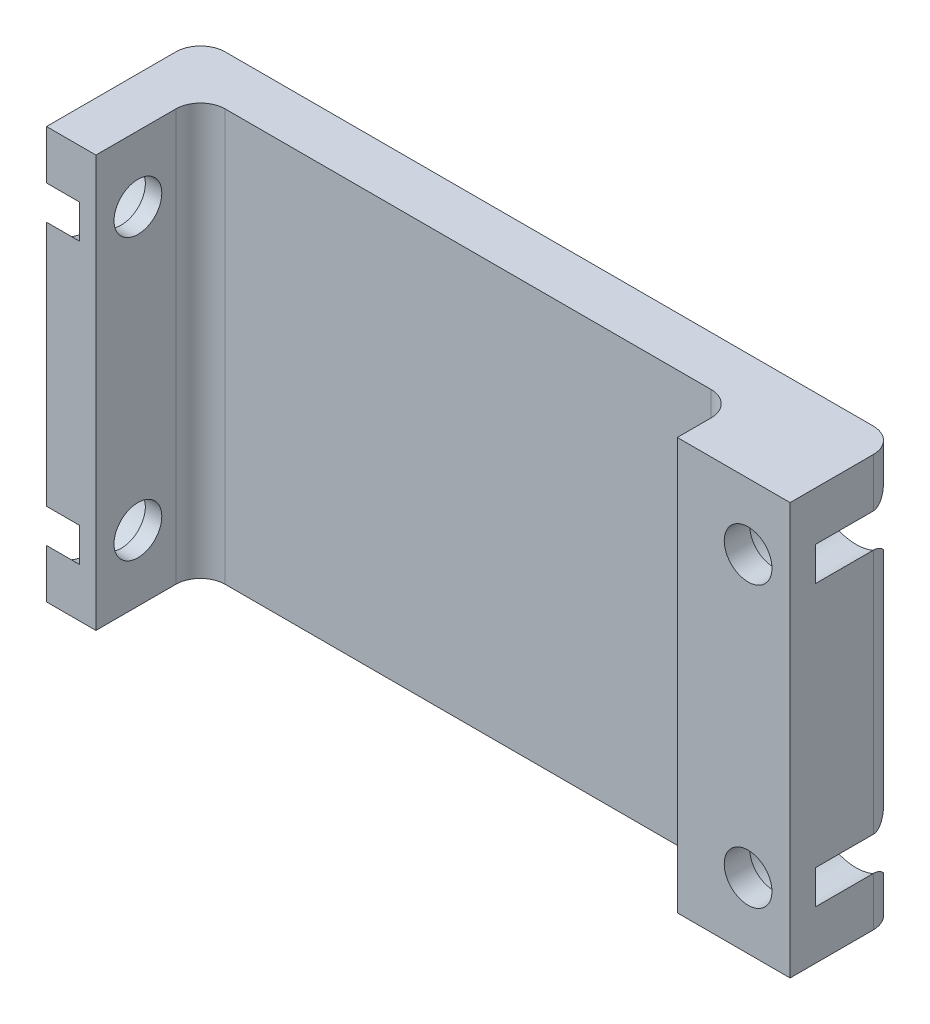
SolidWorks part; units mm, degrees
ref_plane "Plano frontal" through (0, 0, 0) normal (0, 0, 1) x (1, 0, 0)
ref_plane "Plano superior" through (0, 0, 0) normal (0, 1, 0) x (1, 0, 0)
ref_plane "Plano direito" through (0, 0, 0) normal (1, 0, 0) x (0, 0, -1)
sketch "Esboço2" plane through (0, 0, 0) normal (0, 0, 1) x (1, 0, 0)
  line L0 (0, 0) -> (0, -38.6) construction
  line L1 (-1.5, -22.5) -> (5.3501, -22.5)
  line L2 (-1.5, -22.5) -> (-1.5, 2.5)
  line L3 (-1.5, 2.5) -> (5.3501, 2.5)
  line L4 (5.3501, -22.5) -> (5.3501, 2.5)
  line L5 (2.8, -1.5) -> (2.8, 2.5) construction
  line L6 (2.8, -18.5) -> (2.8, -22.5) construction
  dimension "D1" = 0.25
  dimension "D2" = 4
  dimension "D3" = 1.5
extrude "Ressalto-extrusão2" add sketch "Esboço2" against normal offset from surface (3.55 mm away) 1 from offset 0.25 offset beyond the face yes offset against normal yes
sketch "Esboço3" plane through (0, 0, -3.8) normal (0, 0, -1) x (-1, 0, 0)
  line L0 (33.75, 0) -> (33.75, -38.6) construction
  line L1 (-5.3501, 2.5) -> (34, 2.5)
  line L2 (-5.3501, 2.5) -> (-5.3501, -22.5)
  line L3 (-5.3501, -22.5) -> (34, -22.5)
  line L4 (34, 2.5) -> (34, -22.5)
  line L5 (-5.3501, -22.5) -> (1.5, -22.5) construction
  dimension "D1" = 0.25
extrude "Ressalto-extrusão3" add sketch "Esboço3" along normal blind 3
sketch "Esboço4" plane through (-34, 0, 0) normal (-1, 0, 0) x (0, 0, 1)
  line L1 (-6.8, -22.5) -> (2.55, -22.5)
  line L2 (-6.8, -22.5) -> (-6.8, 2.5)
  line L3 (-6.8, 2.5) -> (2.55, 2.5)
  line L4 (2.55, -22.5) -> (2.55, 2.5)
  line L5 (-6.8, 2.5) -> (-3.8, 2.5) construction
  dimension "D1" = 0.25
extrude "Ressalto-extrusão4" add sketch "Esboço4" along normal blind 3
hole_wizard "CBORE for M2.5 SHCS2" positions "3DSketch1" profile "Sketch1" counterbore size "M2.5" standard "ANSI Metric"
sketch3d "3DSketch1"
  circle A0 centre (-33.75, -1.5, 0) radius 1.35 construction
  circle A1 centre (-33.75, -18.5, 0) radius 1.35 construction
  point P0 (-37, -1.5, 0)
  point P7 (-32.4, -1.5, 0)
  point P8 (-37, -18.5, 0)
  point P20 (-32.4, -18.5, 0)
sketch "Sketch1" plane through (-37, -1.5, 0) normal (0, 1, 0) x (0, 0, 1)
  line L0 (0, 0) -> (0, 3.8712)
  line L1 (0, 3.8712) -> (1.45, 3)
  line L2 (1.45, 3) -> (1.45, 2)
  line L3 (1.45, 2) -> (2.75, 2)
  line L4 (2.75, 2) -> (2.75, 0)
  line L5 (2.75, 0) -> (0, 0)
  line L10 (0, 3.8712) -> (-1.45, 3) construction
  line L11 (0, -6.35) -> (0, 107.95) construction
  dimension "Hole Dia." = 2.9
  dimension "Hole Depth" = 3
  dimension "C'Bore Dia." = 5.5
  dimension "C'Bore Depth" = 2
  dimension "Drill Angle" = 118
hole_wizard "CBORE for M2.5 SHCS3" positions "Sketch2" profile "Sketch4" counterbore size "M2.5" standard "ANSI Metric" end condition up to next
sketch "Sketch2" plane through (0, 0, -6.8) normal (0, 0, -1) x (-1, 0, 0)
  circle A0 centre (-2.8, -1.5) radius 1.35 construction
  point P0 (-2.8, -1.5)
  point P6 (-2.8, -18.5)
sketch "Sketch4" plane through (2.8, -1.5, -6.8) normal (1, 0, 0) x (0, 1, 0)
  line L0 (0, 0) -> (0, 6.55)
  line L1 (0, 6.55) -> (1.45, 6.55)
  line L3 (1.45, 6.55) -> (1.45, 5)
  line L4 (1.45, 5) -> (2.75, 5)
  line L5 (2.75, 5) -> (2.75, 0)
  line L7 (2.75, 0) -> (0, 0)
  line L11 (0, -6.35) -> (0, 107.95) construction
  dimension "Thru Hole Dia." = 2.9
  dimension "Thru Hole Depth" = 6.55
  dimension "C'Bore Dia." = 5.5
  dimension "C'Bore Depth" = 5
fillet "Filete1" radius 1.5 6 edges at (-34, -10, -3.8) (-37, -10, -6.8) (5.3501, -21.0147, -6.8) (5.3501, 1.0147, -6.8) (5.3501, -10, -6.8) (-1.5, -10, -3.8)
move or copy body "Corpo-Mover/Copiar1" [suppressed] bodies to move or copy 104
